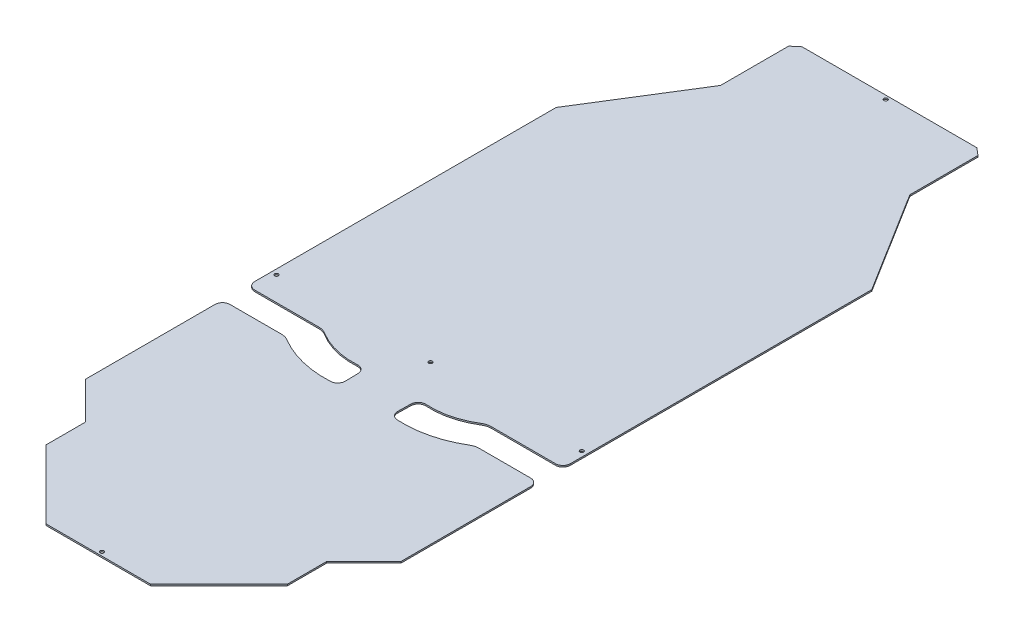
SolidWorks part; units mm, degrees
material "Silicon"
ref_plane "Front Plane" through (0, 0, 0) normal (0, 0, 1) x (1, 0, 0)
ref_plane "Top Plane" through (0, 0, 0) normal (0, 1, 0) x (1, 0, 0)
ref_plane "Right Plane" through (0, 0, 0) normal (1, 0, 0) x (0, 0, -1)
sketch "Sketch1" plane through (0, 0, 0) normal (0, 1, 0) x (1, 0, 0)
  line L0 (-35.2145, -273.75) -> (35.2145, -273.75)
  line L1 (-58.8338, 258.9975) -> (58.8338, 258.9975)
  line L2 (-101.25, -67.1344) -> (-58.0427, -67.1344)
  line L3 (-101.25, -83.874) -> (-66.6054, -83.874)
  line L4 (-106.25, 140.8174) -> (-106.25, -62.1344)
  line L5 (-17.7934, -81.054) -> (-17.6405, -89.8104)
  line L6 (-106.25, -88.874) -> (-106.25, -176.25)
  line L7 (63.7472, -83.874) -> (106.25, -83.874) construction
  line L8 (-33.75, -26.25) -> (-63.7472, -83.874) construction
  line L9 (-18.75, -26.25) -> (-17.5596, -94.4485) construction
  line L10 (0, -1000) -> (0, 49000) construction
  line L11 (-55.0331, -67.1344) -> (-106.25, -67.1344) construction
  line L12 (-63.7472, -83.874) -> (-106.25, -83.874) construction
  line L13 (-1000, 0) -> (49000, 0) construction
  line L14 (-69.6336, 222.2959) -> (-63.7544, 254.8852) construction
  line L15 (-106.25, -176.25) -> (-81.25, -201.25)
  line L16 (-81.25, -201.25) -> (-81.25, -227.7145)
  line L17 (-81.25, -227.7145) -> (-35.2145, -273.75)
  line L18 (55.0331, -67.1344) -> (106.25, -67.1344) construction
  line L19 (81.25, -227.7145) -> (35.2145, -273.75)
  line L20 (81.25, -201.25) -> (81.25, -227.7145)
  line L21 (106.25, -176.25) -> (81.25, -201.25)
  line L22 (-106.25, 140.8174) -> (-63.7544, 208.9975)
  line L23 (106.25, -88.874) -> (106.25, -176.25)
  line L24 (17.7934, -81.054) -> (17.6405, -89.8104)
  line L25 (106.25, 140.8174) -> (106.25, -62.1344)
  line L26 (101.25, -83.874) -> (66.6054, -83.874)
  line L27 (101.25, -67.1344) -> (58.0427, -67.1344)
  line L28 (-63.7544, 208.9975) -> (-63.7544, 254.8852)
  line L29 (-98.75, -210.2145) -> (-42.7145, -266.25) construction
  line L30 (-63.7544, 254.8852) -> (-58.8338, 258.9975)
  line L31 (63.7544, 254.8852) -> (58.8338, 258.9975)
  line L32 (106.25, 140.8174) -> (63.7544, 208.9975)
  line L33 (63.7544, 208.9975) -> (63.7544, 254.8852)
  arc A0 (-52.7439, -68.6537) -> (-23.1069, -76.1511) centre (-26.25, -26.25) ccw
  arc A1 (-61.4809, -85.2868) -> (-22.3566, -94.8897) centre (-26.25, -26.25) ccw
  circle A2 centre (0, 256.5047) radius 1.25
  circle A3 centre (-102.8125, -50.9375) radius 1.25
  arc A4 (-66.6054, -83.874) -> (-61.4809, -85.2868) centre (-66.6054, -93.874) cw
  circle A5 centre (0, -50) radius 1.25
  arc A6 (-58.0427, -67.1344) -> (-52.7439, -68.6537) centre (-58.0427, -77.1344) cw
  arc A7 (-101.25, -67.1344) -> (-106.25, -62.1344) centre (-101.25, -62.1344) cw
  circle A8 centre (-26.25, -26.25) radius 68.75 construction
  arc A9 (-101.25, -83.874) -> (-106.25, -88.874) centre (-101.25, -88.874) ccw
  circle A10 centre (0, -271.25) radius 1.25
  arc A11 (-17.7934, -81.054) -> (-23.1069, -76.1511) centre (-22.7926, -81.1412) ccw
  arc A12 (-17.6405, -89.8104) -> (-22.3566, -94.8897) centre (-22.6398, -89.8977) cw
  arc A13 (-63.7544, 254.8852) -> (-58.8338, 258.9975) centre (-58.8338, 253.9975) cw construction
  circle A14 centre (-26.25, -26.25) radius 7.5 construction
  circle A16 centre (-26.25, -26.25) radius 50 construction
  arc A17 (17.6405, -89.8104) -> (22.3566, -94.8897) centre (22.6398, -89.8977) ccw
  arc A18 (17.7934, -81.054) -> (23.1069, -76.1511) centre (22.7926, -81.1412) cw
  arc A19 (101.25, -83.874) -> (106.25, -88.874) centre (101.25, -88.874) cw
  arc A20 (101.25, -67.1344) -> (106.25, -62.1344) centre (101.25, -62.1344) ccw
  arc A21 (58.0427, -67.1344) -> (52.7439, -68.6537) centre (58.0427, -77.1344) ccw
  arc A22 (66.6054, -83.874) -> (61.4809, -85.2868) centre (66.6054, -93.874) ccw
  circle A23 centre (102.8125, -50.9375) radius 1.25
  arc A24 (61.4809, -85.2868) -> (22.3566, -94.8897) centre (26.25, -26.25) cw
  arc A25 (52.7439, -68.6537) -> (23.1069, -76.1511) centre (26.25, -26.25) cw
  spline S1 degree 3 poles (-69.6336, 222.2959) (-77.5218, 178.5707) (-92.8768, 155.1093) (-106.25, 140.8174) knots 0 0 0 0 0.298944 0.298944 0.298944 0.298944 construction
  point P1 (17.8895, -75.5461)
  point P3 (0, -273.75)
  point P51 (-17.8895, -75.5461)
  point P90 (0, 258.9975)
  dimension "D3" = 137.5
  dimension "D4" = 15
  dimension "D5" = 27.5
  dimension "D7" = 100
  dimension "D1" = 2.5
  dimension "D11" = 10
  dimension "D12" = 5
  dimension "D13" = 5
  dimension "D6" = 28.5
  dimension "D8" = 25
  dimension "D2" = 50
extrude "Boss-Extrude1" add sketch "Sketch1" along normal blind 1
sketch "Sketch2" plane through (0, 0, 0) normal (0, 1, 0) x (1, 0, 0)
  line L0 (-106.25, -176.25) -> (-106.25, -108.874)
  line L1 (106.25, -176.25) -> (106.25, -108.874)
  line L20 (-81.25, -227.7145) -> (-35.2145, -273.75)
  line L21 (-35.2145, -273.75) -> (35.2145, -273.75)
  line L22 (35.2145, -273.75) -> (81.25, -227.7145)
  line L23 (81.25, -227.7145) -> (81.25, -201.25)
  line L24 (81.25, -201.25) -> (106.25, -176.25)
  line L25 (106.25, -176.25) -> (106.25, -88.874)
  line L26 (101.25, -83.874) -> (66.6054, -83.874)
  line L27 (17.6405, -89.8104) -> (17.7934, -81.054)
  line L28 (58.0427, -67.1344) -> (101.25, -67.1344)
  line L29 (106.25, -62.1344) -> (106.25, 140.8174)
  line L30 (106.25, 140.8174) -> (63.7544, 208.9975)
  line L31 (58.8338, 258.9975) -> (-58.8338, 258.9975)
  line L32 (106.25, 140.8174) -> (63.7544, 208.9975)
  line L33 (-106.25, 140.8174) -> (-106.25, -62.1344)
  line L34 (-101.25, -67.1344) -> (-58.0427, -67.1344)
  line L35 (-17.7934, -81.054) -> (-17.6405, -89.8104)
  line L36 (-66.6054, -83.874) -> (-101.25, -83.874)
  line L37 (-106.25, -88.874) -> (-106.25, -176.25)
  line L38 (-106.25, -176.25) -> (-81.25, -201.25)
  line L39 (-81.25, -201.25) -> (-81.25, -227.7145)
  line L40 (-81.25, -227.7145) -> (-35.2145, -273.75)
  line L41 (-35.2145, -273.75) -> (35.2145, -273.75)
  line L42 (35.2145, -273.75) -> (81.25, -227.7145)
  line L43 (81.25, -227.7145) -> (81.25, -201.25)
  line L44 (81.25, -201.25) -> (106.25, -176.25)
  line L46 (101.25, -103.874) -> (66.6054, -103.874)
  line L52 (63.7544, 208.9975) -> (63.7544, 254.8852)
  line L53 (63.7544, 208.9975) -> (63.7544, 254.8852)
  line L54 (63.7544, 254.8852) -> (58.8338, 258.9975)
  line L55 (63.7544, 254.8852) -> (58.8338, 258.9975)
  line L56 (-66.6054, -103.874) -> (-101.25, -103.874)
  line L57 (-58.8338, 258.9975) -> (-63.7544, 254.8852)
  line L58 (-106.25, -176.25) -> (-81.25, -201.25)
  line L59 (-81.25, -201.25) -> (-81.25, -227.7145)
  line L60 (-58.8338, 258.9975) -> (-63.7544, 254.8852)
  line L61 (-63.7544, 254.8852) -> (-63.7544, 208.9975)
  line L62 (-63.7544, 254.8852) -> (-63.7544, 208.9975)
  line L63 (-63.7544, 208.9975) -> (-106.25, 140.8174)
  line L64 (-63.7544, 208.9975) -> (-106.25, 140.8174)
  arc A0 (-61.4809, -105.2868) -> (61.4809, -105.2868) centre (0, -2.2626) ccw
  arc A18 (106.25, -88.874) -> (101.25, -83.874) centre (101.25, -88.874) ccw
  arc A19 (66.6054, -83.874) -> (61.4809, -85.2868) centre (66.6054, -93.874) ccw
  arc A20 (22.3566, -94.8897) -> (61.4809, -85.2868) centre (26.25, -26.25) ccw
  arc A21 (17.6405, -89.8104) -> (22.3566, -94.8897) centre (22.6398, -89.8977) ccw
  arc A22 (23.1069, -76.1511) -> (17.7934, -81.054) centre (22.7926, -81.1412) ccw
  arc A23 (23.1069, -76.1511) -> (52.7439, -68.6537) centre (26.25, -26.25) ccw
  arc A24 (58.0427, -67.1344) -> (52.7439, -68.6537) centre (58.0427, -77.1344) ccw
  arc A25 (101.25, -67.1344) -> (106.25, -62.1344) centre (101.25, -62.1344) ccw
  arc A28 (-106.25, -62.1344) -> (-101.25, -67.1344) centre (-101.25, -62.1344) ccw
  arc A29 (-52.7439, -68.6537) -> (-58.0427, -67.1344) centre (-58.0427, -77.1344) ccw
  arc A30 (-52.7439, -68.6537) -> (-23.1069, -76.1511) centre (-26.25, -26.25) ccw
  arc A31 (-17.7934, -81.054) -> (-23.1069, -76.1511) centre (-22.7926, -81.1412) ccw
  arc A32 (-22.3566, -94.8897) -> (-17.6405, -89.8104) centre (-22.6398, -89.8977) ccw
  arc A33 (-61.4809, -85.2868) -> (-22.3566, -94.8897) centre (-26.25, -26.25) ccw
  arc A34 (-61.4809, -85.2868) -> (-66.6054, -83.874) centre (-66.6054, -93.874) ccw
  arc A35 (-101.25, -83.874) -> (-106.25, -88.874) centre (-101.25, -88.874) ccw
  arc A36 (106.25, -108.874) -> (101.25, -103.874) centre (101.25, -108.874) ccw
  arc A37 (66.6054, -103.874) -> (61.4809, -105.2868) centre (66.6054, -113.874) ccw
  arc A52 (-61.4809, -105.2868) -> (-66.6054, -103.874) centre (-66.6054, -113.874) ccw
  arc A53 (-101.25, -103.874) -> (-106.25, -108.874) centre (-101.25, -108.874) ccw
  dimension "D1" = 0
extrude "Boss-Extrude2" [suppressed] add sketch "Sketch2" along normal blind 1 from offset 10 separate body
sketch "Sketch4" [suppressed] plane through (0, 10, 0) normal (0, -1, 0) x (1, 0, 0)
  line L0 (106.25, 273.75) -> (131.25, 256.25) construction
  line L3 (104.8163, 271.7019) -> (106.25, 273.75)
  line L4 (129.8163, 254.2019) -> (131.25, 256.25)
  line L5 (106.25, 273.75) -> (131.25, 256.25)
  line L6 (0, -1000) -> (0, 49000) construction
  line L7 (-103.75, 108.874) -> (-106.25, 108.874)
  line L8 (104.8163, 271.7019) -> (129.8163, 254.2019)
  line L9 (101.25, 106.374) -> (101.25, 103.874)
  line L10 (103.75, 108.874) -> (106.25, 108.874)
  line L11 (-101.25, 106.374) -> (-101.25, 103.874)
  line L12 (103.75, 181.25) -> (103.75, 108.874) construction
  line L13 (106.25, 181.25) -> (106.25, 108.874) construction
  line L14 (101.25, 106.374) -> (66.6054, 106.374) construction
  line L15 (101.25, 103.874) -> (66.6054, 103.874) construction
  line L16 (-104.8163, 271.7019) -> (-129.8163, 254.2019)
  line L17 (-106.25, 273.75) -> (-131.25, 256.25)
  line L18 (-129.8163, 254.2019) -> (-131.25, 256.25)
  line L19 (-104.8163, 271.7019) -> (-106.25, 273.75)
  arc A0 (101.25, 103.874) -> (106.25, 108.874) centre (101.25, 108.874) ccw construction
  arc A1 (101.25, 103.874) -> (106.25, 108.874) centre (101.25, 108.874) ccw
  arc A2 (101.25, 106.374) -> (103.75, 108.874) centre (101.25, 108.874) ccw
  arc A3 (-101.25, 106.374) -> (-103.75, 108.874) centre (-101.25, 108.874) cw
  arc A4 (-101.25, 103.874) -> (-106.25, 108.874) centre (-101.25, 108.874) cw
  dimension "D1" = 2.5
extrude "Boss-Extrude3" [suppressed] add sketch "Sketch4" along normal up to body
